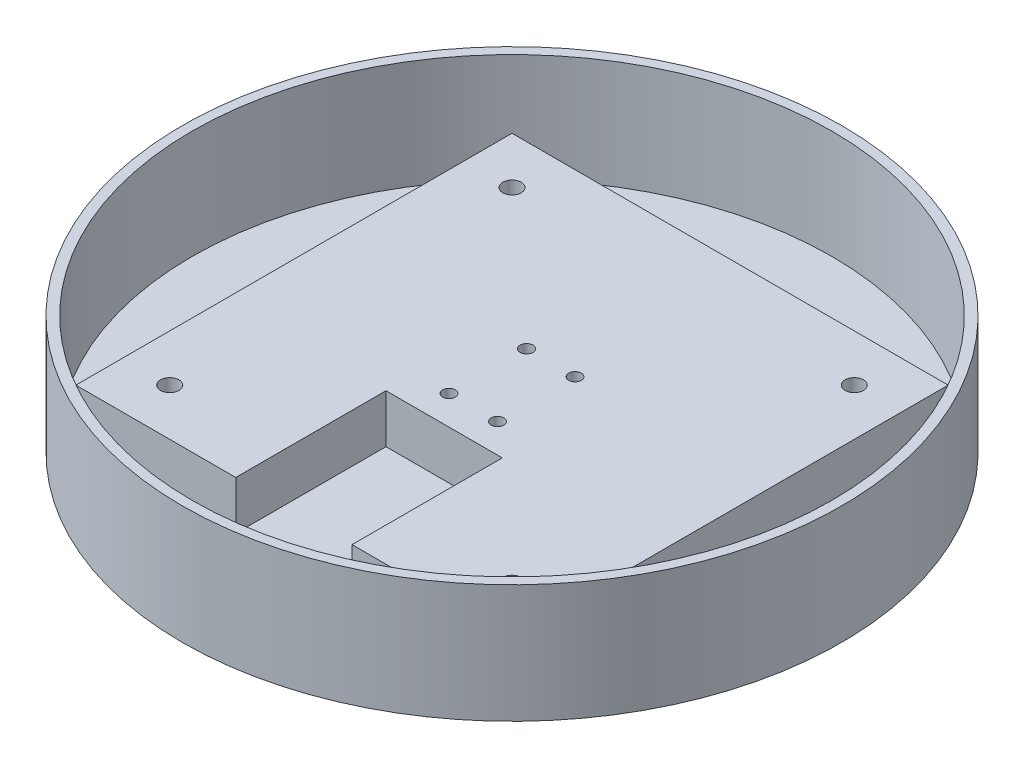
SolidWorks part; units mm, degrees
ref_plane "Front Plane" through (0, 0, 0) normal (0, 0, 1) x (1, 0, 0)
ref_plane "Top Plane" through (0, 0, 0) normal (0, 1, 0) x (1, 0, 0)
ref_plane "Right Plane" through (0, 0, 0) normal (1, 0, 0) x (0, 0, -1)
sketch "Sketch1" plane through (0, 0, 0) normal (0, 1, 0) x (1, 0, 0)
  circle A0 centre (0, 0) radius 83.82
  circle A1 centre (0, 0) radius 86.36
  dimension "D1" = 167.64
  dimension "D2" = 2.54
extrude "Boss-Extrude1" add sketch "Sketch1" along normal blind 28.45
extrude "Boss-Extrude2" add sketch "Sketch1<2>" against normal blind 2.54 contours A0 | A1 A0
sketch "Sketch1<2>" plane through (0, 0, 0) normal (0, 1, 0) x (1, 0, 0) same geometry as "Sketch1"
sketch "Sketch2" plane through (0, 0, 0) normal (0, 1, 0) x (1, 0, 0)
  line L1 (-44.845, -44.845) -> (-15.24, -44.845) construction
  line L2 (-44.845, -44.845) -> (-44.845, -42.432) construction
  line L3 (-44.845, 44.845) -> (44.845, 44.845) construction
  line L4 (44.845, -44.845) -> (44.845, 44.845) construction
  line L5 (-44.845, -44.845) -> (-43.1388, -43.1388) construction
  line L6 (-44.845, 44.845) -> (-43.1388, 43.1388) construction
  line L7 (-57.15, -57.15) -> (-15.24, -57.15)
  line L8 (-57.15, -57.15) -> (-57.15, 57.15)
  line L9 (-57.15, 57.15) -> (57.15, 57.15)
  line L10 (57.15, -57.15) -> (57.15, 57.15)
  line L11 (-57.15, -57.15) -> (-43.1388, -43.1388) construction
  line L12 (-57.15, 57.15) -> (-43.1388, 43.1388) construction
  line L20 (-15.24, -17.78) -> (-15.24, -57.15)
  line L22 (15.24, -17.78) -> (15.24, -57.15)
  line L23 (43.1388, -43.1388) -> (57.15, -57.15) construction
  line L24 (43.1388, -43.1388) -> (44.845, -44.845) construction
  line L25 (15.24, -57.15) -> (57.15, -57.15)
  line L26 (15.24, -44.845) -> (44.845, -44.845) construction
  line L27 (-15.24, -17.78) -> (15.24, -17.78)
  line L28 (-44.845, 42.432) -> (-44.845, 44.845) construction
  line L29 (43.1388, 43.1388) -> (44.845, 44.845) construction
  line L30 (43.1388, 43.1388) -> (57.15, 57.15) construction
  circle A0 centre (44.845, 44.845) radius 2.413
  circle A1 centre (44.845, -44.845) radius 2.413
  circle A2 centre (-44.845, -44.845) radius 2.413
  circle A3 centre (-44.845, 44.845) radius 2.413
  point P0 (0, 0)
  point P6 (0, 0)
  point P15 (0, 0)
  dimension "D3" = 4.826
  dimension "D4" = 4.826
  dimension "D5" = 4.826
  dimension "D6" = 4.826
  dimension "D1" = 89.69
  dimension "D2" = 114.3
extrude "Boss-Extrude3" add sketch "Sketch2" along normal blind 12.7
sketch "Sketch3" plane through (0, 12.7, 0) normal (0, 1, 0) x (1, 0, 0)
  line L11 (-6.35, -10.16) -> (6.35, -10.16) construction
  line L12 (-6.35, -10.16) -> (-6.35, 10.16) construction
  line L13 (-6.35, 10.16) -> (6.35, 10.16) construction
  line L14 (6.35, -10.16) -> (6.35, 10.16) construction
  line L15 (-6.35, -10.16) -> (6.35, 10.16) construction
  line L16 (-6.35, 10.16) -> (6.35, -10.16) construction
  circle A0 centre (6.35, 10.16) radius 1.651
  circle A1 centre (6.35, -10.16) radius 1.651
  circle A2 centre (-6.35, -10.16) radius 1.651
  circle A3 centre (-6.35, 10.16) radius 1.6813
  circle A4 centre (0, 0) radius 83.82 construction
  circle A5 centre (0, 0) radius 83.82 construction
  point P4 (0, 0)
  dimension "D3" = 3.302
  dimension "D4" = 3.302
  dimension "D5" = 3.302
  dimension "D6" = 3.3626
  dimension "D1" = 12.7
  dimension "D2" = 20.32
extrude "Cut-Extrude1" cut sketch "Sketch3" against normal blind 2.54
